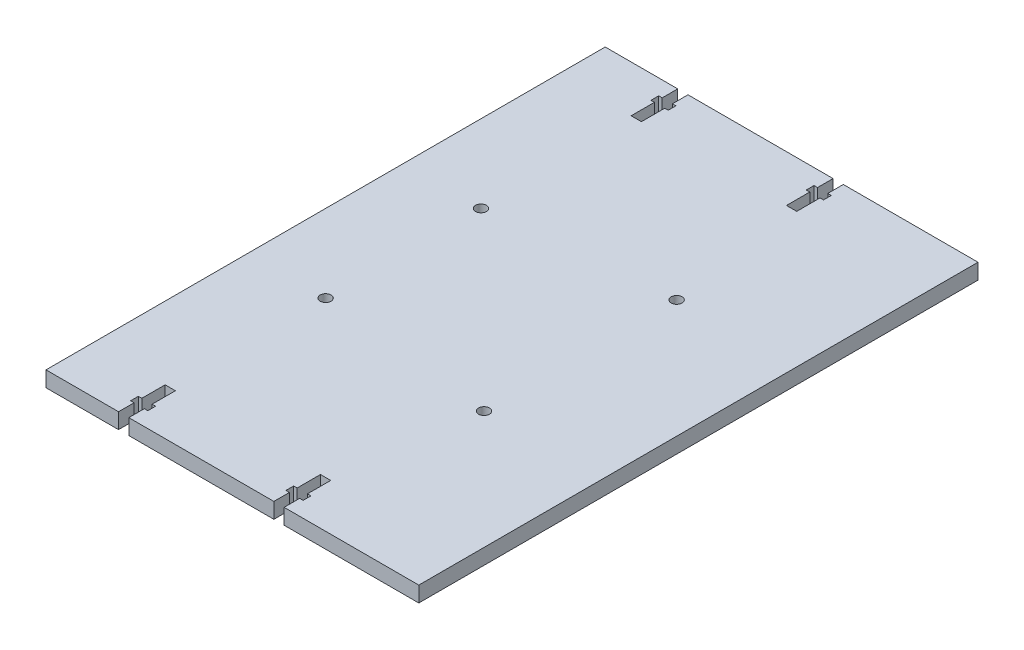
SolidWorks part; units mm, degrees
ref_plane "Front Plane" through (0, 0, 0) normal (0, 0, 1) x (1, 0, 0)
ref_plane "Top Plane" through (0, 0, 0) normal (0, 1, 0) x (1, 0, 0)
ref_plane "Right Plane" through (0, 0, 0) normal (1, 0, 0) x (0, 0, -1)
sketch "Sketch1" plane through (0, 0, 0) normal (0, 1, 0) x (1, 0, 0)
  line L1 (0, 0) -> (120, 0)
  line L2 (0, 0) -> (0, 180)
  line L3 (0, 180) -> (120, 180)
  line L4 (120, 0) -> (120, 180)
  dimension "D1" = 180
  dimension "D2" = 120
extrude "Boss-Extrude1" add sketch "Sketch1" along normal blind 5
sketch "Sketch2" plane through (0, 5, 0) normal (0, 1, 0) x (1, 0, 0)
  line L0 (0, 0) -> (120, 0) construction
  line L1 (23.35, 15) -> (26.65, 15)
  line L2 (23.35, 15) -> (23.35, 7.5)
  line L3 (23.35, 0) -> (26.65, 0)
  line L4 (26.65, 15) -> (26.65, 7.5)
  line L5 (26.65, 5) -> (27.775, 5)
  line L6 (22.225, 7.5) -> (23.35, 7.5)
  line L7 (22.225, 7.5) -> (22.225, 5)
  line L8 (22.225, 5) -> (23.35, 5)
  line L9 (27.775, 7.5) -> (27.775, 5)
  line L10 (26.65, 7.5) -> (27.775, 7.5)
  line L11 (23.35, 5) -> (23.35, 0)
  line L12 (26.65, 5) -> (26.65, 0)
  line L13 (25, 15) -> (25, 0) construction
  line L14 (0, 180) -> (0, 0) construction
  line L15 (-1000, 90) -> (49000, 90) construction
  line L16 (50, -819.8321) -> (50, 49174.3228) construction
  line L18 (76.65, 15) -> (76.65, 7.5)
  line L19 (77.775, 7.5) -> (76.65, 7.5)
  line L20 (77.775, 7.5) -> (77.775, 5)
  line L21 (77.775, 5) -> (76.65, 5)
  line L22 (76.65, 5) -> (76.65, 0)
  line L23 (76.65, 0) -> (73.35, 0)
  line L24 (73.35, 5) -> (73.35, 0)
  line L25 (73.35, 5) -> (72.225, 5)
  line L26 (72.225, 7.5) -> (72.225, 5)
  line L27 (73.35, 7.5) -> (72.225, 7.5)
  line L28 (73.35, 15) -> (73.35, 7.5)
  line L29 (76.65, 15) -> (73.35, 15)
  line L30 (76.65, 165) -> (73.35, 165)
  line L31 (73.35, 165) -> (73.35, 172.5)
  line L32 (73.35, 172.5) -> (72.225, 172.5)
  line L33 (72.225, 172.5) -> (72.225, 175)
  line L34 (73.35, 175) -> (72.225, 175)
  line L35 (73.35, 175) -> (73.35, 180)
  line L36 (76.65, 180) -> (73.35, 180)
  line L37 (76.65, 175) -> (76.65, 180)
  line L38 (77.775, 175) -> (76.65, 175)
  line L39 (77.775, 172.5) -> (77.775, 175)
  line L40 (77.775, 172.5) -> (76.65, 172.5)
  line L41 (76.65, 165) -> (76.65, 172.5)
  line L42 (23.35, 165) -> (23.35, 172.5)
  line L43 (22.225, 172.5) -> (23.35, 172.5)
  line L44 (22.225, 172.5) -> (22.225, 175)
  line L45 (22.225, 175) -> (23.35, 175)
  line L46 (23.35, 175) -> (23.35, 180)
  line L47 (23.35, 180) -> (26.65, 180)
  line L48 (26.65, 175) -> (26.65, 180)
  line L49 (26.65, 175) -> (27.775, 175)
  line L50 (27.775, 172.5) -> (27.775, 175)
  line L51 (26.65, 172.5) -> (27.775, 172.5)
  line L52 (26.65, 165) -> (26.65, 172.5)
  line L53 (23.35, 165) -> (26.65, 165)
  point P10 (22.225, 6.25)
  point P28 (0, 90)
  dimension "D1" = 15
  dimension "D2" = 3.3
  dimension "D3" = 5.55
  dimension "D4" = 2.5
  dimension "D5" = 5
  dimension "D6" = 5.55
  dimension "D7" = 25
  dimension "D8" = 50
extrude "Cut-Extrude1" cut sketch "Sketch2" against normal blind 5
sketch "Sketch3" plane through (0, 5, 0) normal (0, 1, 0) x (1, 0, 0)
  line L0 (82, 121) -> (82, 59) construction
  line L1 (25, 115) -> (25, 65) construction
  line L2 (0, 180) -> (0, 0) construction
  circle A0 centre (25, 65) radius 1.75
  circle A1 centre (82, 59) radius 1.75
  circle A2 centre (25, 115) radius 1.75
  circle A3 centre (82, 121) radius 1.75
  point P7 (25, 90)
  point P10 (82, 90)
  point P14 (0, 90)
  dimension "D1" = 3.5
  dimension "D4" = 50
  dimension "D5" = 62
  dimension "D2" = 25
  dimension "D3" = 57
extrude "Cut-Extrude2" cut sketch "Sketch3" against normal blind 5
